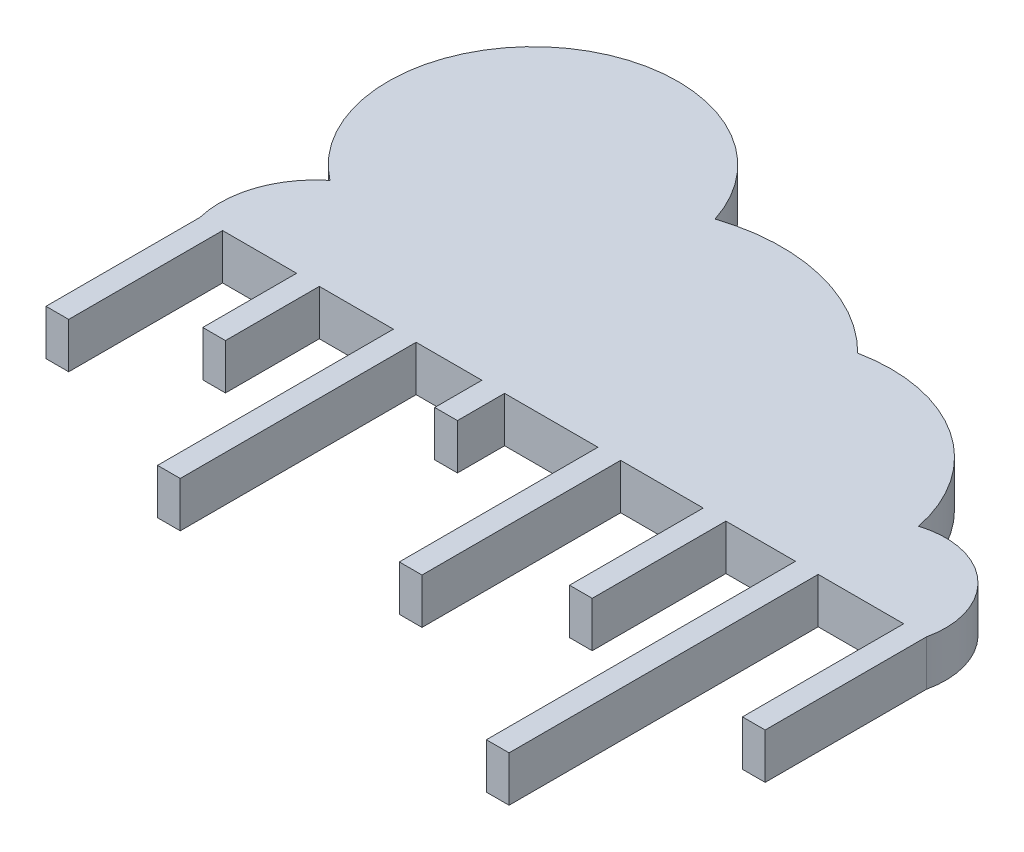
SolidWorks part; units mm, degrees
ref_plane "Front Plane" through (0, 0, 0) normal (0, 0, 1) x (1, 0, 0)
ref_plane "Top Plane" through (0, 0, 0) normal (0, 1, 0) x (1, 0, 0)
ref_plane "Right Plane" through (0, 0, 0) normal (1, 0, 0) x (0, 0, -1)
sketch "Sketch1" plane through (0, 0, 0) normal (0, 1, 0) x (1, 0, 0)
  line L0 (0, 0) -> (101.6, 0)
  arc A0 (0, 0) -> (18.8591, 15.1948) centre (13.0015, 3.1641) cw
  arc A1 (18.8591, 15.1948) -> (62.4404, 29.559) centre (44.2509, 11.4511) cw
  arc A2 (62.4404, 29.559) -> (87.651, 12.8496) centre (66.691, 8.599) cw
  arc A3 (87.651, 12.8496) -> (101.6, 0) centre (90.9343, 2.4178) cw
  dimension "D1" = 101.6
extrude "cloud" add sketch "Sketch1" along normal blind 6.35
sketch "Sketch2" plane through (0, 0, 0) normal (0, 1, 0) x (1, 0, 0)
  arc A0 (4.6063, 13.5838) -> (36.2165, 35.8274) centre (16.9285, 29.6551) cw
  arc A1 (18.8591, 15.1948) -> (0, 0) centre (13.0015, 3.1641) ccw construction
  arc A2 (62.4404, 29.559) -> (18.8591, 15.1948) centre (44.2509, 11.4511) ccw construction
  arc A3 (18.8591, 15.1948) -> (4.6063, 13.5838) centre (13.0015, 3.1641) ccw
  arc A4 (36.2165, 35.8274) -> (18.8591, 15.1948) centre (44.2509, 11.4511) ccw
extrude "Boss-Extrude2" add sketch "Sketch2" along normal blind 6.35
sketch "Sketch3" plane through (0, 0, 0) normal (0, 1, 0) x (1, 0, 0)
  line L0 (0, 0) -> (101.6, 0) construction
  line L2 (0, 0) -> (3.175, 0)
  line L3 (0, 0) -> (0, -21.521)
  line L4 (0, -21.521) -> (3.175, -21.521)
  line L5 (3.175, 0) -> (3.175, -21.521)
  line L6 (101.6, 0) -> (98.425, 0)
  line L7 (101.6, 0) -> (101.6, -22.551)
  line L8 (101.6, -22.551) -> (98.425, -22.551)
  line L9 (98.425, 0) -> (98.425, -22.551)
  line L10 (73.5626, 0) -> (70.3876, 0)
  line L11 (73.5626, 0) -> (73.5626, -18.6977)
  line L12 (73.5626, -18.6977) -> (70.3876, -18.6977)
  line L13 (70.3876, 0) -> (70.3876, -18.6977)
  line L15 (39.436, 0) -> (42.611, 0)
  line L16 (39.436, 0) -> (39.436, -6.5932)
  line L17 (39.436, -6.5932) -> (42.611, -6.5932)
  line L18 (42.611, 0) -> (42.611, -6.5932)
  line L19 (58.8386, 0) -> (55.6636, 0)
  line L20 (58.8386, 0) -> (58.8386, -27.776)
  line L21 (58.8386, -27.776) -> (55.6636, -27.776)
  line L22 (55.6636, 0) -> (55.6636, -27.776)
  line L23 (13.5251, 0) -> (16.7001, 0)
  line L24 (13.5251, 0) -> (13.5251, -13.1233)
  line L25 (13.5251, -13.1233) -> (16.7001, -13.1233)
  line L26 (16.7001, 0) -> (16.7001, -13.1233)
  line L27 (86.4634, 0) -> (83.2884, 0)
  line L28 (86.4634, 0) -> (86.4634, -43.2251)
  line L29 (86.4634, -43.2251) -> (83.2884, -43.2251)
  line L30 (83.2884, 0) -> (83.2884, -43.2251)
  line L31 (27.0641, 0) -> (30.2391, 0)
  line L32 (27.0641, 0) -> (27.0641, -32.9866)
  line L33 (27.0641, -32.9866) -> (30.2391, -32.9866)
  line L34 (30.2391, 0) -> (30.2391, -32.9866)
  dimension "D1" = 3.175
  dimension "D2" = 3.175
  dimension "D3" = 3.175
  dimension "D4" = 3.175
  dimension "D5" = 3.175
  dimension "D6" = 3.175
  dimension "D7" = 3.175
  dimension "D8" = 3.175
extrude "Boss-Extrude3" add sketch "Sketch3" along normal blind 6.35
shell "Shell1" thickness 0.635 removed face at (49.5509, 0, 6.8325)
